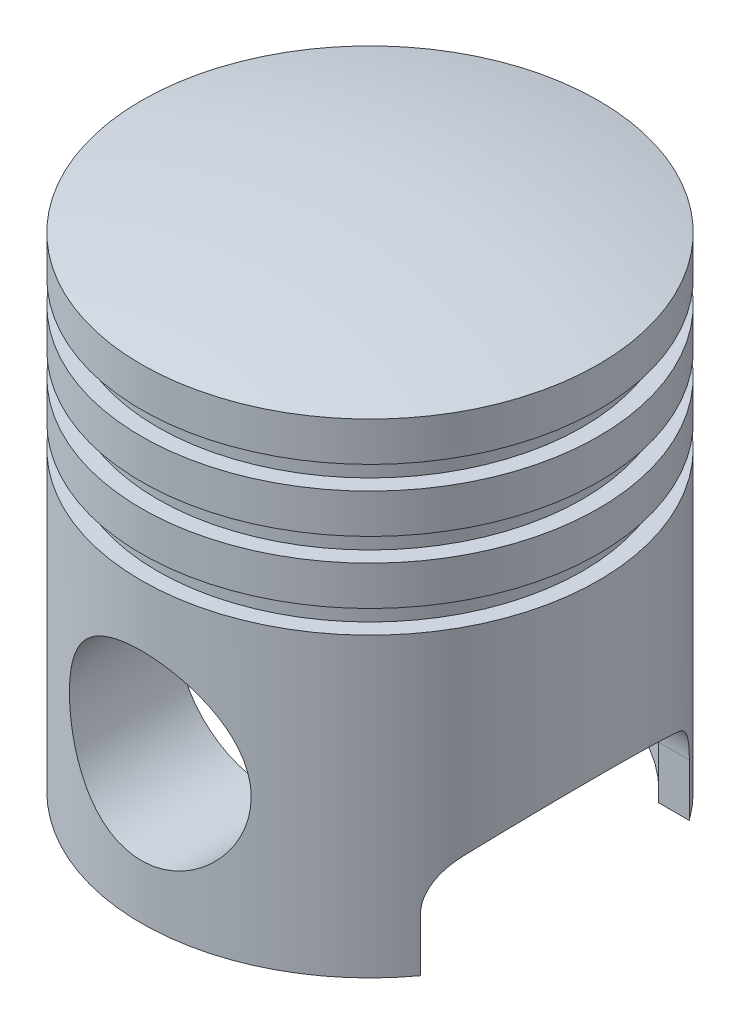
SolidWorks part; units mm, degrees
ref_plane "Front Plane" through (0, 0, 0) normal (0, 0, 1) x (1, 0, 0)
ref_plane "Top Plane" through (0, 0, 0) normal (0, 1, 0) x (1, 0, 0)
ref_plane "Right Plane" through (0, 0, 0) normal (1, 0, 0) x (0, 0, -1)
sketch "Sketch1" plane through (0, 0, 0) normal (0, 1, 0) x (1, 0, 0)
  circle A0 centre (0, 0) radius 42.5
  dimension "D1" = 85
extrude "Boss-Extrude1" add sketch "Sketch1" along normal blind 90
sketch "Sketch2" plane through (0, 90, 0) normal (0, 1, 0) x (1, 0, 0)
  circle A0 centre (0, 0) radius 39.5
  dimension "D1" = 79
extrude "Cut-Extrude1" cut sketch "Sketch2" against normal blind 4.3 from offset 7.3 flip side to cut offset against normal yes
pattern_linear "LPattern1" count 3 spacing 11.6 along (0, -1, 0) of "Cut-Extrude1"
sketch "Sketch3" plane through (0, 0, 0) normal (0, -1, 0) x (1, 0, 0)
  circle A0 centre (0, 0) radius 38
  dimension "D1" = 76
extrude "Cut-Extrude2" cut sketch "Sketch3" against normal blind 85
dome "Dome1" faces to dome 1 distance 5 reverse direction no elliptical dome no face at (0, 90, 42.5) parameters "D1"=5
sketch "Sketch4" plane through (0, 0, 0) normal (0, 0, 1) x (1, 0, 0)
  circle A0 centre (0, 27) radius 16.9
  point P2 (0, 0)
  dimension "D1" = 33.8
  dimension "D2" = 27
extrude "Cut-Extrude3" cut sketch "Sketch4" against normal through all and the other way through all
sketch "Sketch5" plane through (0, 0, 0) normal (1, 0, 0) x (0, 0, -1)
  line L0 (0, 0) -> (0, 48.0701) construction
  line L1 (-25, 0) -> (-25, 15.0068)
  line L2 (-42.5, 0) -> (42.5, 0) construction
  line L3 (25, 0) -> (25, 15.0068)
  arc A0 (-25, 15.0068) -> (25, 15.0068) centre (0, -16.2182) cw
  dimension "D2" = 40
  dimension "D1" = 50
extrude "Cut-Extrude4" cut sketch "Sketch5" against normal through all both and the other way through all
fillet "Fillet1" radius 10 2 edges at (31.4937, 15.0068, 25) (31.4937, 15.0068, -25)
fillet "Fillet2" radius 10 2 edges at (-31.4937, 15.0068, -25) (-31.4937, 15.0068, 25)
sketch "Sketch6" plane through (0, 0, 0) normal (0, 0, 1) x (1, 0, 0)
  circle A0 centre (0, 27) radius 22.5
  circle A1 centre (0, 27) radius 16.9 construction
  circle A2 centre (0, 27) radius 16.9
  dimension "D1" = 45
extrude "Boss-Extrude2" add sketch "Sketch6" against normal up to next from offset 19 offset against normal yes
mirror "Mirror1" about plane through (0, 0, 0) normal (0, 0, 1) of "Boss-Extrude2"
